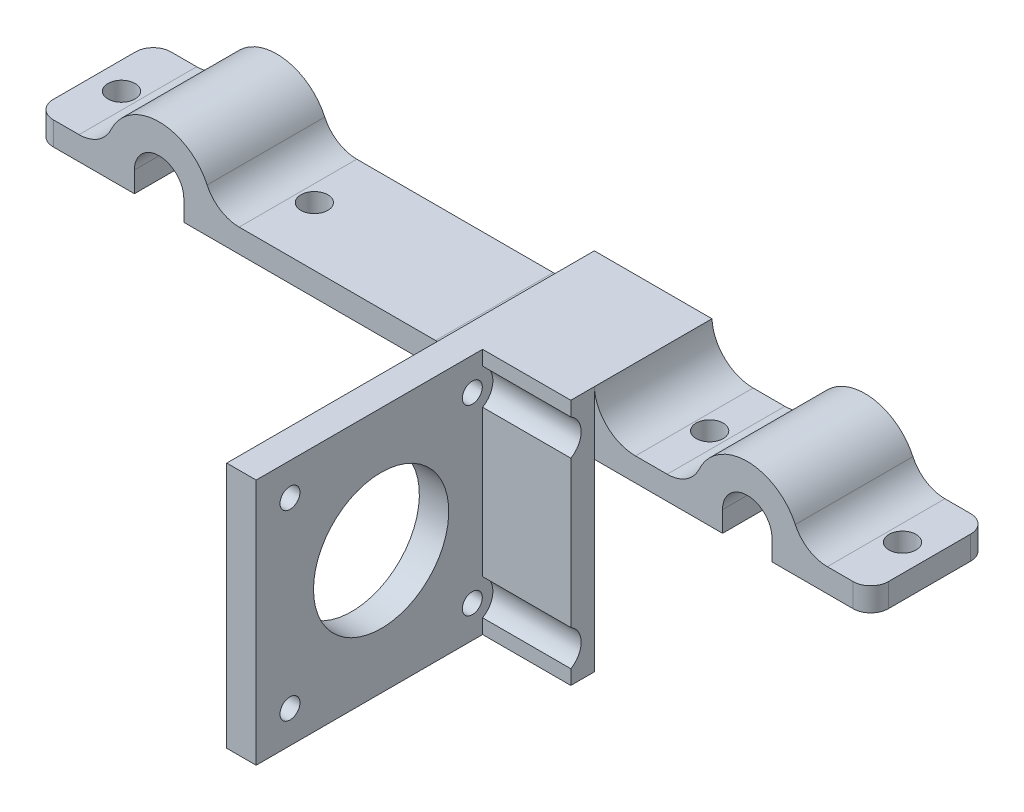
SolidWorks part; units mm, degrees
ref_plane "前视基准面" through (0, 0, 0) normal (0, 0, 1) x (1, 0, 0)
ref_plane "上视基准面" through (0, 0, 0) normal (0, 1, 0) x (1, 0, 0)
ref_plane "右视基准面" through (0, 0, 0) normal (1, 0, 0) x (0, 0, -1)
sketch "草图1" plane through (0, 0, 0) normal (0, 0, 1) x (1, 0, 0)
  line L0 (-1000, 0) -> (49000, 0) construction
  line L1 (0, -1000) -> (0, 49000) construction
  line L2 (54.2, 3.8) -> (54.2, 0.3)
  line L3 (54.2, 0.3) -> (70.995, 0.3)
  line L4 (70.995, 0.3) -> (70.995, 4.3)
  line L5 (70.995, 4.3) -> (63.6129, 4.3)
  line L6 (-36.3871, 4.3) -> (36.3871, 4.3)
  line L7 (-45.8, 0.3) -> (45.8, 0.3)
  line L8 (45.8, 0.3) -> (45.8, 3.8)
  line L9 (1000, 0) -> (-49000, 0) construction
  line L10 (-45.8, 0.3) -> (-45.8, 3.8)
  line L11 (-70.995, 4.3) -> (-63.6129, 4.3)
  line L12 (-70.995, 0.3) -> (-70.995, 4.3)
  line L13 (-54.2, 0.3) -> (-70.995, 0.3)
  line L14 (-54.2, 3.8) -> (-54.2, 0.3)
  circle A0 centre (50, 4) radius 4 construction
  arc A1 (54.2, 3.8) -> (45.8, 3.8) centre (50, 3.8) ccw
  circle A2 centre (-50, 4) radius 4 construction
  arc A3 (58.1677, 7.78) -> (41.8323, 7.78) centre (50, 4) ccw
  arc A4 (-58.1677, 7.78) -> (-41.8323, 7.78) centre (-50, 4) cw
  arc A5 (-54.2, 3.8) -> (-45.8, 3.8) centre (-50, 3.8) cw
  arc A6 (-41.8323, 7.78) -> (-36.3871, 4.3) centre (-36.3871, 10.3) ccw
  arc A7 (-58.1677, 7.78) -> (-63.6129, 4.3) centre (-63.6129, 10.3) cw
  arc A8 (36.3871, 4.3) -> (41.8323, 7.78) centre (36.3871, 10.3) ccw
  arc A9 (63.6129, 4.3) -> (58.1677, 7.78) centre (63.6129, 10.3) cw
  point P17 (0, 4.3)
  point P28 (0, 0.3)
  point P33 (-41.005, 4.3)
  point P36 (-58.995, 4.3)
  point P39 (41.005, 4.3)
  point P42 (58.995, 4.3)
  dimension "D1" = 8
  dimension "D2" = 8.4
  dimension "D3" = 9
  dimension "D8" = 6
  dimension "D4" = 0.3
  dimension "D5" = 4
  dimension "D6" = 12
  dimension "D7" = 100
  dimension "D9" = 20.995
extrude "凸台-拉伸1" add sketch "草图1" along normal blind 20
fillet "圆角1" radius 3 4 edges at (70.995, 2.3, 20) (70.995, 2.3, 0) (-70.995, 2.3, 0) (-70.995, 2.3, 20)
sketch "草图2" plane through (0, 4.3, 0) normal (0, 1, 0) x (1, 0, 0)
  line L0 (0, -1000) -> (0, 49000) construction
  line L1 (36.3871, 0) -> (-36.3871, 0) construction
  line L2 (50, -1000) -> (50, 49000) construction
  line L3 (58.1677, 0) -> (41.8323, 0) construction
  line L5 (70.995, -17) -> (70.995, -3) construction
  circle A0 centre (0, -10) radius 2.7 construction
  circle A1 centre (66.395, -10) radius 2.3
  circle A2 centre (33.605, -10) radius 2.3
  circle A3 centre (-33.605, -10) radius 2.3
  circle A4 centre (-66.395, -10) radius 2.3
  point P7 (0, 0)
  point P12 (50, 0)
  dimension "D1" = 5.4
  dimension "D3" = 4.6
  dimension "D2" = 10
  dimension "D4" = 4.6
extrude "切除-拉伸1" cut sketch "草图2" against normal through all and the other way through all
sketch "草图3" plane through (0, 0, 20) normal (0, 0, 1) x (1, 0, 0)
  line L0 (36.3871, 4.3) -> (-36.3871, 4.3) construction
  line L1 (24, -31) -> (4, -31)
  line L2 (24, -31) -> (24, 4.3)
  line L3 (24, 4.3) -> (4, 4.3)
  line L4 (4, -31) -> (4, 4.3)
  line L5 (24, -31) -> (4, 4.3) construction
  line L6 (24, 4.3) -> (4, -31) construction
  point P0 (14, -13.35)
  dimension "D1" = 31
  dimension "D2" = 20
  dimension "D3" = 4
extrude "凸台-拉伸2" add sketch "草图3" along normal blind 4
sketch "草图4" plane through (0, 0, 24) normal (0, 0, 1) x (1, 0, 0)
  line L1 (4, -31) -> (9, -31)
  line L2 (4, -31) -> (4, 11)
  line L3 (4, 11) -> (9, 11)
  line L4 (9, -31) -> (9, 11)
  dimension "D1" = 11
  dimension "D2" = 5
extrude "凸台-拉伸3" add sketch "草图4" along normal blind 38.5
sketch "草图5" plane through (0, 4.3, 0) normal (0, 1, 0) x (1, 0, 0)
  line L0 (4, -24) -> (4, -13)
  line L1 (36.3871, 0) -> (-36.3871, 0) construction
  line L2 (4, 0) -> (24, 0)
  line L4 (24, 0) -> (24, -24)
  line L5 (24, -24) -> (4, -24)
  line L7 (4, -13) -> (4, 0)
extrude "凸台-拉伸4" add sketch "草图5" along normal up to surface (6.7 mm away) up to face at (6.5, 11, 43.25)
sketch "草图6" plane through (24, 0, 0) normal (1, 0, 0) x (0, 0, -1)
  line L0 (-62.5, -10) -> (-20, -10) construction
  line L1 (-62.5, -31) -> (-62.5, 11) construction
  line L2 (-20, -31) -> (-20, 0.3) construction
  line L3 (-22, 11) -> (-22, -31) construction
  line L4 (-62.5, 11) -> (-24, 11) construction
  line L5 (-24, -31) -> (-20, -31) construction
  line L6 (-25.75, 5.5) -> (-41.25, -10) construction
  circle A0 centre (-41.25, -10) radius 11.5
  circle A1 centre (-25.75, 5.5) radius 1.7
  circle A2 centre (-25.75, -25.5) radius 1.7
  circle A3 centre (-56.75, -25.5) radius 1.7
  circle A4 centre (-56.75, 5.5) radius 1.7
  point P25 (-41.25, -10)
  dimension "D1" = 23
  dimension "D2" = 3.4
  dimension "D5" = 31
  dimension "D3" = 45
  dimension "D4" = 4
extrude "切除-拉伸2" cut sketch "草图6" against normal up to next
fillet "圆角2" radius 7 4 edges at (4, 4.3, 10) (24, 7.65, 0) (24, 4.3, 10) (4, 7.65, 0)
sketch "草图7" plane through (0, 0, 20) normal (0, 0, -1) x (-1, 0, 0)
  line L0 (-24, -31) -> (-24, 0.3) construction
  line L1 (-24, -7.2) -> (-4, -7.2)
  line L2 (-24, -7.2) -> (-24, -12.8)
  line L3 (-24, -12.8) -> (-4, -12.8)
  line L4 (-4, -7.2) -> (-4, -12.8)
  line L5 (-4, 0.3) -> (-4, -31) construction
  dimension "D1" = 5.6
  dimension "D2" = 7.2
extrude "凸台-拉伸5" [suppressed] add sketch "草图7" along normal blind 5
sketch "草图9" plane through (9, 0, 0) normal (1, 0, 0) x (0, 0, -1)
  circle A0 centre (-25.75, 5.5) radius 3.5
  circle A1 centre (-25.75, -25.5) radius 3.5
  dimension "D1" = 7
  dimension "D2" = 7
extrude "切除-拉伸3" cut sketch "草图9" along normal up to next contours A0 | A1
sketch "草图10" plane through (0, 0.3, 0) normal (0, -1, 0) x (1, 0, 0)
  line L0 (-33.605, 10) -> (33.605, 10) construction
  line L1 (12, 13) -> (23.605, 13)
  line L2 (12, 13) -> (12, 7)
  line L3 (12, 7) -> (23.605, 7)
  line L4 (23.605, 13) -> (23.605, 7)
  line L5 (0, 0) -> (0, 10) construction
  line L6 (-23.605, 13) -> (-23.605, 7)
  line L7 (-12, 7) -> (-23.605, 7)
  line L8 (-12, 13) -> (-12, 7)
  line L9 (-12, 13) -> (-23.605, 13)
  dimension "D1" = 6
  dimension "D2" = 12
  dimension "D3" = 10
extrude "凸台-拉伸6" add sketch "草图10" along normal blind 5
